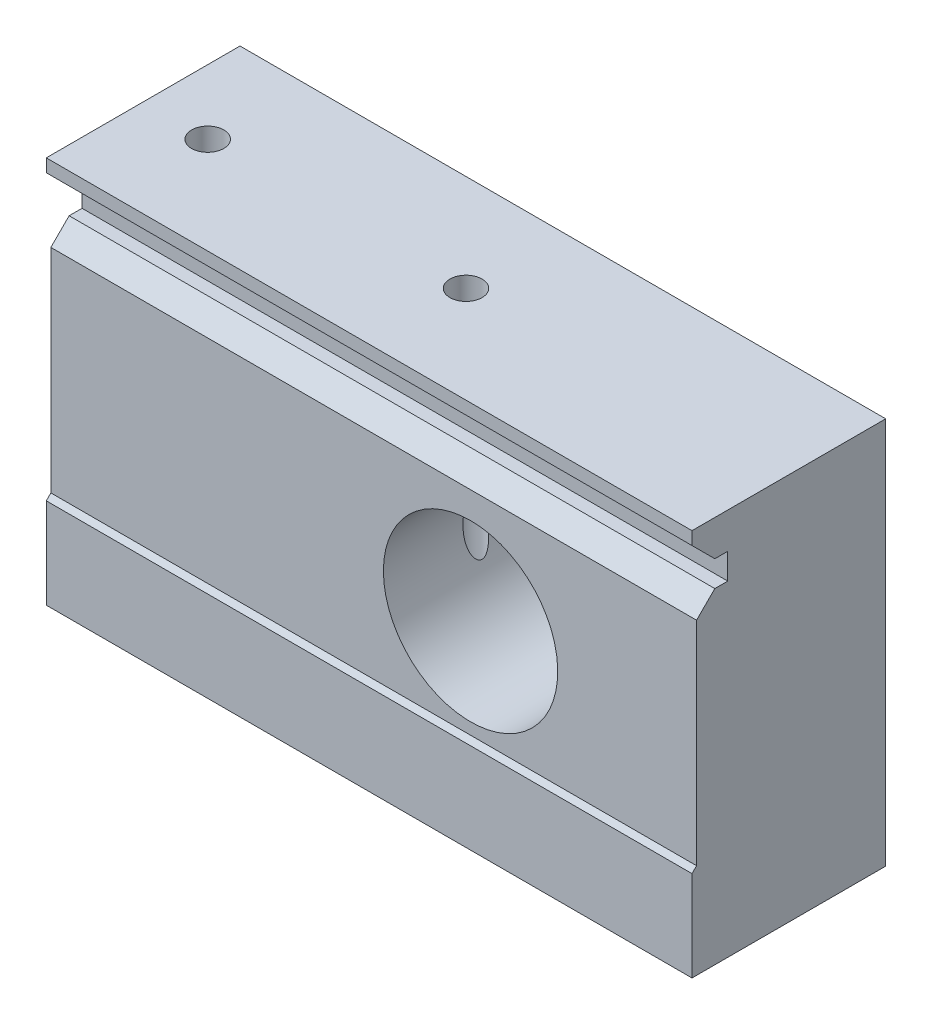
SolidWorks part; units mm, degrees
ref_plane "Front Plane" through (0, 0, 0) normal (0, 0, 1) x (1, 0, 0)
ref_plane "Top Plane" through (0, 0, 0) normal (0, 1, 0) x (1, 0, 0)
ref_plane "Right Plane" through (0, 0, 0) normal (1, 0, 0) x (0, 0, -1)
sketch "Sketch1" plane through (0, 0, 0) normal (0, 0, 1) x (1, 0, 0)
  line L1 (-47.9208, 29.5149) -> (52.0792, 29.5149)
  line L2 (-47.9208, 29.5149) -> (-47.9208, -30.4851)
  line L3 (-47.9208, -30.4851) -> (52.0792, -30.4851)
  line L4 (52.0792, 29.5149) -> (52.0792, -30.4851)
  dimension "D1" = 100
  dimension "D2" = 60
extrude "Boss-Extrude1" add sketch "Sketch1" along normal blind 30
sketch "Sketch3" plane through (-47.9208, 0, 0) normal (-1, 0, 0) x (0, 0, 1)
  line L10 (30, -30.4851) -> (30, -16.4851)
  line L11 (30, 29.5149) -> (30, -30.4851) construction
  line L12 (30, -16.4851) -> (29.2929, -15.778)
  line L13 (29.2929, -15.778) -> (29.2929, 17.1509)
  line L14 (29.2929, 17.1509) -> (26.4645, 19.9793)
  line L15 (26.4645, 19.9793) -> (24.4645, 19.9793)
  line L16 (24.4645, 19.9793) -> (24.4645, 23.9793)
  line L17 (24.4645, 23.9793) -> (26.4645, 23.9793)
  line L18 (26.4645, 23.9793) -> (30, 27.5149)
  line L19 (30, 27.5149) -> (30, 29.5149)
  line L20 (30, 29.5149) -> (35.631, 28.6016)
  line L21 (35.631, 28.6016) -> (37.1491, -26.2478)
  line L22 (37.1491, -26.2478) -> (30, -30.4851)
  dimension "D1" = 2
  dimension "D2" = 4
  dimension "D3" = 5
  dimension "D4" = 4
  dimension "D5" = 2
  dimension "D6" = 135
  dimension "D7" = 14
extrude "Cut-Extrude1" cut sketch "Sketch3" against normal blind 110
sketch "Эскиз1" plane through (0, 29.5149, 0) normal (0, 1, 0) x (1, 0, 0)
  line L0 (52.0792, 0) -> (-47.9208, 0) construction
  line L1 (52.0792, -30) -> (52.0792, 0) construction
  circle A0 centre (2.0792, -15) radius 2.4933
  dimension "D2" = 50
  dimension "D1" = 15
extrude "Вырез-Вытянуть1" cut sketch "Эскиз1" against normal blind 100
pattern_linear "Линейный массив1" count 2 spacing 40 along (-1, 0, 0) of "Вырез-Вытянуть1"
sketch "Эскиз2" plane through (0, 0, 0) normal (0, 0, -1) x (-1, 0, 0)
  line L0 (-52.0792, 29.5149) -> (47.9208, 29.5149) construction
  line L1 (-52.0792, -30.4851) -> (-52.0792, 29.5149) construction
  circle A0 centre (-17.0792, -0.4851) radius 13.5
  dimension "D1" = 30
  dimension "D2" = 35
extrude "Вырез-Вытянуть2" cut sketch "Эскиз2" against normal blind 100
